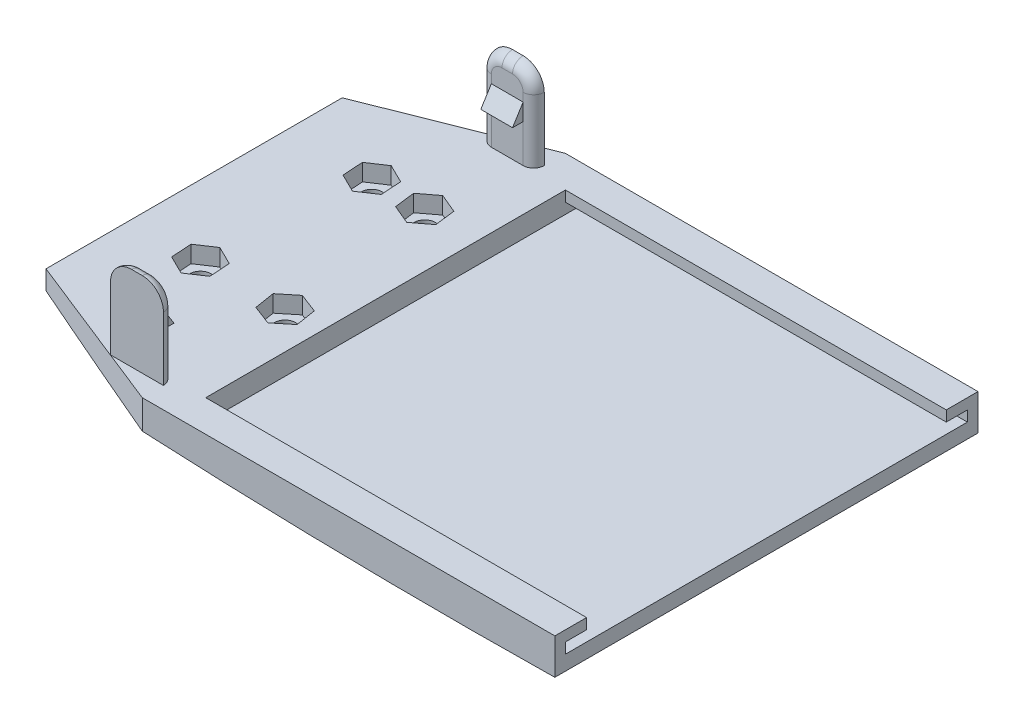
SolidWorks part; units mm, degrees
material "1060 Alloy"
ref_plane "Front Plane" through (0, 0, 0) normal (0, 0, 1) x (1, 0, 0)
ref_plane "Top Plane" through (0, 0, 0) normal (0, 1, 0) x (1, 0, 0)
ref_plane "Right Plane" through (0, 0, 0) normal (1, 0, 0) x (0, 0, -1)
sketch "Sketch1" plane through (0, 0, 0) normal (0, 1, 0) x (1, 0, 0)
  line L1 (-135.25, -100) -> (135.25, -100)
  line L2 (-135.25, -100) -> (-135.25, 100)
  line L3 (-135.25, 100) -> (135.25, 100)
  line L4 (135.25, -100) -> (135.25, 100)
  point P4 (-135.25, 0)
  point P5 (0, 0)
  point P6 (135.25, 0)
  point P7 (0, -100)
  point P9 (0, 100)
  dimension "D1" = 270.5
  dimension "D2" = 200
extrude "MainBody" add sketch "Sketch1" along normal blind 9
sketch "Sketch5" plane through (0, 9, 0) normal (0, 1, 0) x (1, 0, 0)
  line L0 (-135.25, 0) -> (90.5, 0) construction
  line L1 (-135.25, 100) -> (-135.25, -100) construction
  line L3 (-102.25, 0) -> (-102.25, -30) construction
  line L4 (-95.25, 0) -> (-95.25, 44) construction
  line L5 (-70.25, 0) -> (-70.25, 44) construction
  line L6 (-62.25, 0) -> (-62.25, -30) construction
  circle A1 centre (-102.25, -30) radius 5
  circle A2 centre (-95.25, 44) radius 5
  circle A3 centre (-70.25, 44) radius 5
  circle A4 centre (-62.25, -30) radius 5
  dimension "D1" = 33
  dimension "D9" = 10
  dimension "D10" = 10
  dimension "D11" = 10
  dimension "D12" = 10
  dimension "D2" = 30
  dimension "D3" = 40
  dimension "D4" = 44
  dimension "D5" = 65
  dimension "D6" = 44
  dimension "D7" = 73
  dimension "D8" = 30
ref_plane "Plane1" through (0, 0, 0) normal (0, 0, 1) x (1, 0, 0)
sketch "Sketch12" plane through (0, 0, 0) normal (0, 0, 1) x (1, 0, 0)
  line L3 (-135.25, 0) -> (135.25, 0) construction
  line L5 (135.25, 0) -> (135.25, -7.9767)
  line L11 (-135.25, 0) -> (135.25, 0)
  arc A10 (-135.25, 0) -> (135.25, -7.9767) centre (87.25, 2954.7745) ccw
  point P2 (0, 0)
  point P6 (0, 0)
  point P7 (0, 0)
  dimension "D1" = 270.5
  dimension "D2" = 2963.14
  dimension "D3" = 222.5
extrude "MainBodyCurve" add sketch "Sketch12" along normal blind 100 and the other way blind 100
extrude "BoltHole" cut sketch "Sketch5" against normal through all and the other way through all
sketch "Sketch13" plane through (0, 9, 0) normal (0, 1, 0) x (1, 0, 0)
  line L13 (-87.084, 49.4451) -> (-95.8826, 53.7945)
  line L14 (-95.8826, 53.7945) -> (-104.0486, 48.3494)
  line L15 (-104.0486, 48.3494) -> (-103.416, 38.5549)
  line L16 (-103.416, 38.5549) -> (-94.6174, 34.2055)
  line L17 (-94.6174, 34.2055) -> (-86.4514, 39.6506)
  line L18 (-86.4514, 39.6506) -> (-87.084, 49.4451)
  line L19 (-62.4304, 49.9319) -> (-71.4774, 53.7379)
  line L20 (-71.4774, 53.7379) -> (-79.297, 47.806)
  line L21 (-79.297, 47.806) -> (-78.0696, 38.0681)
  line L22 (-78.0696, 38.0681) -> (-69.0226, 34.2621)
  line L23 (-69.0226, 34.2621) -> (-61.203, 40.194)
  line L24 (-61.203, 40.194) -> (-62.4304, 49.9319)
  line L25 (-94.084, -24.5549) -> (-102.8826, -20.2055)
  line L26 (-102.8826, -20.2055) -> (-111.0486, -25.6506)
  line L27 (-111.0486, -25.6506) -> (-110.416, -35.4451)
  line L28 (-110.416, -35.4451) -> (-101.6174, -39.7945)
  line L29 (-101.6174, -39.7945) -> (-93.4514, -34.3494)
  line L30 (-93.4514, -34.3494) -> (-94.084, -24.5549)
  line L31 (-54.6304, -23.8133) -> (-63.798, -20.3079)
  line L32 (-63.798, -20.3079) -> (-71.4176, -26.4946)
  line L33 (-71.4176, -26.4946) -> (-69.8696, -36.1867)
  line L34 (-69.8696, -36.1867) -> (-60.702, -39.6921)
  line L35 (-60.702, -39.6921) -> (-53.0824, -33.5054)
  line L36 (-53.0824, -33.5054) -> (-54.6304, -23.8133)
  circle A0 centre (-95.25, 44) radius 8.5 construction
  circle A1 centre (-95.25, 44) radius 5 construction
  circle A2 centre (-70.25, 44) radius 8.5 construction
  circle A3 centre (-70.25, 44) radius 5 construction
  circle A4 centre (-102.25, -30) radius 8.5 construction
  circle A5 centre (-102.25, -30) radius 5 construction
  circle A6 centre (-62.25, -30) radius 8.5 construction
  circle A7 centre (-62.25, -30) radius 5 construction
  dimension "D1" = 17
  dimension "D2" = 17
  dimension "D3" = 17
  dimension "D4" = 17
extrude "BoltHexHole" cut sketch "Sketch13" against normal blind 8
sketch "Sketch15" plane through (135.25, 0, 0) normal (1, 0, 0) x (0, 0, -1)
  line L0 (-100, 9) -> (100, 9) construction
  line L1 (-85, 14) -> (85, 14)
  line L2 (-95, 4) -> (-95, -1)
  line L3 (-95, -1) -> (95, -1)
  line L4 (95, 4) -> (95, -1)
  line L6 (-95, 4) -> (-85, 4)
  line L9 (-85, 4) -> (-85, 14)
  line L10 (95, 4) -> (85, 4)
  line L13 (85, 4) -> (85, 14)
  point P0 (0, 14)
  dimension "D1" = 170
  dimension "D2" = 190
  dimension "D3" = 10
  dimension "D4" = 10
  dimension "D6" = 10
  dimension "D7" = 5
  dimension "D8" = 5
extrude "SlideCut" cut sketch "Sketch15" against normal blind 180
sketch "Sketch18" plane through (0, 9, 0) normal (0, 1, 0) x (1, 0, 0)
  line L0 (-44.75, 85) -> (-44.75, -85) construction
  line L1 (-201.9773, 0) -> (236.7476, 0) construction
  line L3 (-59.75, -85) -> (-59.75, -90)
  line L8 (-84.75, 85) -> (-59.75, 85)
  line L9 (-84.75, 85) -> (-84.75, 90)
  line L10 (-84.75, 90) -> (-59.75, 90)
  line L11 (-59.75, 85) -> (-59.75, 90)
  line L13 (-84.75, -90) -> (-59.75, -90)
  line L14 (-84.75, -85) -> (-84.75, -90)
  line L15 (-84.75, -85) -> (-59.75, -85)
  dimension "D1" = 5
  dimension "D2" = 85
  dimension "D4" = 15
  dimension "D5" = 25
extrude "Tabs" add sketch "Sketch18" along normal blind 40
sketch "Sketch19" plane through (0, 0, 85) normal (0, 0, -1) x (-1, 0, 0)
  line L1 (79.75, 27) -> (64.75, 27)
  line L2 (79.75, 27) -> (79.75, 35)
  line L3 (79.75, 35) -> (64.75, 35)
  line L4 (64.75, 27) -> (64.75, 35)
  line L6 (72.25, 49) -> (72.25, 9) construction
  line L7 (59.75, 49) -> (84.75, 49) construction
  line L8 (59.75, 9) -> (84.75, 9) construction
  point P12 (72.25, 35)
  dimension "D1" = 15
  dimension "D2" = 8
  dimension "D3" = 18
extrude "TabTriangle1" add sketch "Sketch19" along normal blind 5
sketch "Sketch20" plane through (-79.75, 0, 0) normal (-1, 0, 0) x (0, 0, 1)
  line L0 (85, 35) -> (80, 27)
  line L1 (80, 27) -> (80, 35)
  line L2 (80, 35) -> (85, 35)
  point P4 (0, 0)
extrude "TabTriangleCut1" cut sketch "Sketch20" against normal up to next
fillet "Fillet1" radius 10 2 edges at (-59.75, 49, 87.5) (-84.75, 49, 87.5)
fillet "Fillet2" radius 5 5 edges at (-84.75, 24, 85) (-59.75, 24, 85) (-62.6789, 46.0711, 85) (-72.25, 49, 85) (-81.8211, 46.0711, 85)
sketch "Sketch21" plane through (0, 0, -85) normal (0, 0, 1) x (1, 0, 0)
  line L0 (-84.75, 9) -> (-59.75, 9) construction
  line L1 (-64.75, 27) -> (-79.75, 27)
  line L2 (-64.75, 27) -> (-64.75, 35)
  line L3 (-64.75, 35) -> (-79.75, 35)
  line L4 (-79.75, 27) -> (-79.75, 35)
  line L5 (-84.75, 49) -> (-84.75, 9) construction
  dimension "D1" = 15
  dimension "D2" = 8
  dimension "D3" = 18
  dimension "D4" = 5
extrude "TabTriangle2" add sketch "Sketch21" along normal blind 5
sketch "Sketch22" plane through (-79.75, 0, 0) normal (-1, 0, 0) x (0, 0, 1)
  line L0 (-80, 27) -> (-85, 35)
  line L3 (-80, 27) -> (-80, 35)
  line L4 (-80, 35) -> (-85, 35)
extrude "TabTriangleCut2" cut sketch "Sketch22" against normal up to next
fillet "Fillet3" radius 10 2 edges at (-59.75, 49, -87.5) (-84.75, 49, -87.5)
fillet "Fillet4" radius 5 5 edges at (-59.75, 24, -85) (-62.6789, 46.0711, -85) (-72.25, 49, -85) (-84.75, 24, -85) (-81.8211, 46.0711, -85)
sketch "Sketch27" plane through (0, 9, 0) normal (0, 1, 0) x (1, 0, 0)
  line L0 (-59.75, 100) -> (-59.75, -100) construction
  line L1 (135.25, 100) -> (-135.25, 100) construction
  line L2 (-135.25, -100) -> (135.25, -100) construction
  line L3 (-59.75, 100) -> (-135.25, 70)
  line L4 (-135.25, 100) -> (-135.25, -100) construction
  line L5 (-135.25, 70) -> (-135.25, 100)
  line L6 (-135.25, 100) -> (-59.75, 100)
  line L7 (-59.75, -100) -> (-135.25, -70)
  line L8 (-135.25, -70) -> (-135.25, -100)
  line L9 (-135.25, -100) -> (-59.75, -100)
  dimension "D1" = 30
  dimension "D2" = 30
extrude "Cut-Extrude15" cut sketch "Sketch27" against normal through all
